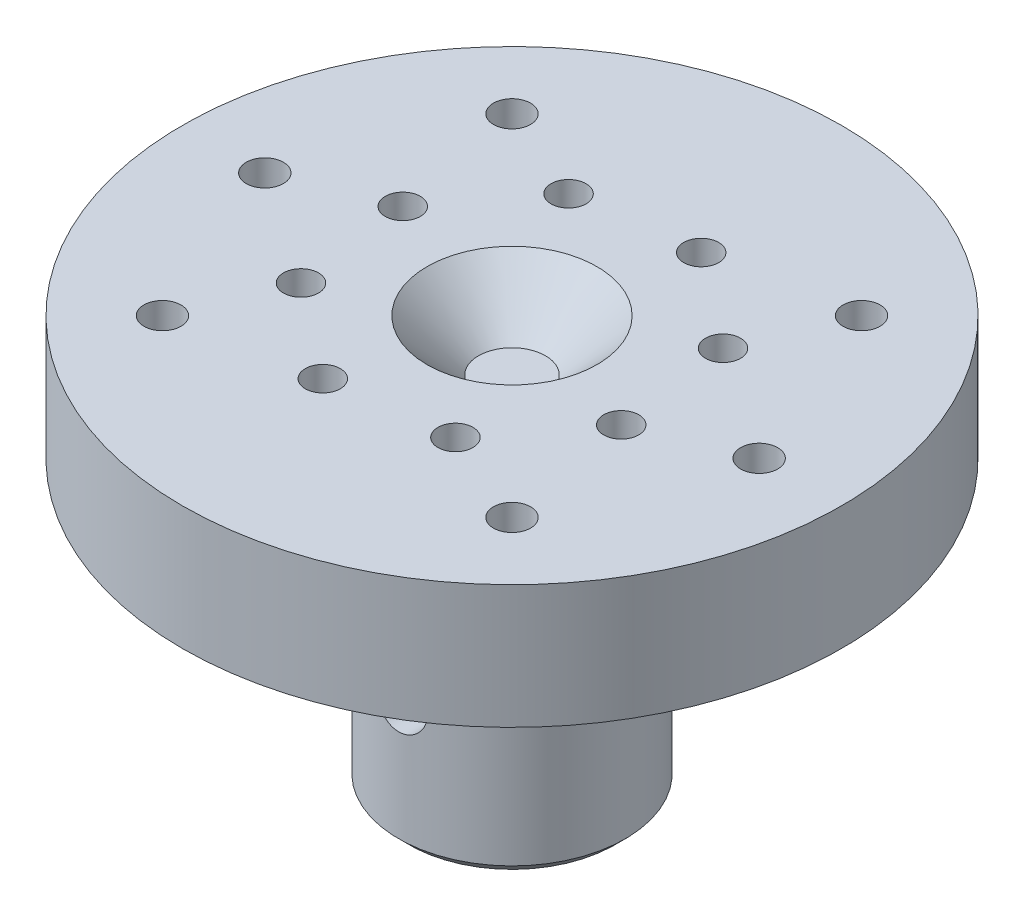
SolidWorks part; units mm, degrees
ref_plane "Front Plane" through (0, 0, 0) normal (0, 0, 1) x (1, 0, 0)
ref_plane "Top Plane" through (0, 0, 0) normal (0, 1, 0) x (1, 0, 0)
ref_plane "Right Plane" through (0, 0, 0) normal (1, 0, 0) x (0, 0, -1)
sketch "Sketch1" plane through (0, 0, 0) normal (0, 1, 0) x (1, 0, 0)
  circle A0 centre (0, 0) radius 8.25
  circle A1 centre (0, 0) radius 32
  dimension "D1" = 16.5
  dimension "D2" = 64
extrude "Boss-Extrude1" add sketch "Sketch1" along normal blind 12
sketch "Sketch2" plane through (0, 12, 0) normal (0, 1, 0) x (1, 0, 0)
  circle A0 centre (0, 21) radius 4
  circle A1 centre (0, 0) radius 21 construction
  circle A2 centre (18.1865, 10.5) radius 4
  circle A3 centre (18.1865, -10.5) radius 4
  circle A4 centre (0, -21) radius 4
  circle A5 centre (-18.1865, -10.5) radius 4
  circle A6 centre (-18.1865, 10.5) radius 4
  point P17 (0, 0)
  dimension "D1" = 8
  dimension "D2" = 42
  dimension "D3" = 6
extrude "Cut-Extrude1" [suppressed] cut sketch "Sketch2" against normal through all and the other way through all
hole_wizard "CSK for M3 Hex Socket Countersunk Head Screw1" positions "Sketch3" profile "Sketch4" countersink size "M3" standard "DIN" end condition up to next
sketch "Sketch3" plane through (0, 0, 0) normal (0, 1, 0) x (1, 0, 0)
  line L0 (0, 0) -> (32.7202, 18.891) construction
  circle A0 centre (0, 0) radius 15
  point P8 (12.9904, 7.5)
  point P14 (14.4889, -3.8823)
  point P15 (7.5, -12.9904)
  point P16 (-3.8823, -14.4889)
  point P17 (-12.9904, -7.5)
  point P18 (-14.4889, 3.8823)
  point P19 (-7.5, 12.9904)
  point P20 (3.8823, 14.4889)
  dimension "D2" = 30
  dimension "D1" = 30
  dimension "D3" = 8
sketch "Sketch4" plane through (3.8823, 0, -14.4889) normal (1, 0, 0) x (0, 0, -1)
  line L0 (0, 0) -> (0, 12)
  line L1 (0, 12) -> (1.7, 12)
  line L2 (1.7, 12) -> (1.7, 1.05)
  line L3 (1.7, 1.05) -> (2.75, 0)
  line L5 (2.75, 0) -> (0, 0)
  line L6 (-1.7, 1.05) -> (-2.75, 0) construction
  line L11 (0, -6.35) -> (0, 107.95) construction
  dimension "Thru Hole Dia." = 3.4
  dimension "Thru Hole Depth" = 12
  dimension "Near C'Sink Dia." = 5.5
  dimension "Near C'Sink Angle" = 90
hole_wizard "CSK for M3 Hex Socket Countersunk Head Screw2" positions "Sketch5" profile "Sketch7" countersink size "M3" standard "DIN"
sketch "Sketch5" plane through (0, 0, 0) normal (0, -1, 0) x (-1, 0, 0)
  circle A0 centre (0, 0) radius 24
  point P6 (-24, 0)
  point P14 (-16.9706, 16.9706)
  point P16 (16.9706, 16.9706)
  point P17 (24, 0)
  point P18 (16.9706, -16.9706)
  point P22 (-16.9706, -16.9706)
  point P25 (0, 24) [skipped]
  point P27 (0, -24) [skipped]
  dimension "D1" = 48
  dimension "D2" = 8
sketch "Sketch7" plane through (16.9706, 0, 16.9706) normal (1, 0, 0) x (0, 0, -1)
  line L0 (0, 0) -> (0, 12)
  line L1 (0, 12) -> (1.8, 12)
  line L2 (1.8, 12) -> (1.8, 1.67)
  line L3 (1.8, 1.67) -> (3.47, 0)
  line L5 (3.47, 0) -> (0, 0)
  line L6 (-1.8, 1.67) -> (-3.47, 0) construction
  line L11 (0, -6.35) -> (0, 107.95) construction
  dimension "Thru Hole Dia." = 3.6
  dimension "Thru Hole Depth" = 12
  dimension "Near C'Sink Dia." = 6.94
  dimension "Near C'Sink Angle" = 90
hole_wizard "Ø3.2 (3.2) Diameter Hole1" [suppressed] positions "Sketch8" profile "Sketch9" hole size "Ø3.2" standard "DIN"
sketch "Sketch8" plane through (0, 0, 0) normal (0, -1, 0) x (-1, 0, 0)
  circle A0 centre (0, 0) radius 15
  point P5 (0, 15)
  point P12 (12.9904, 7.5)
  point P13 (12.9904, -7.5)
  point P14 (0, -15)
  point P15 (-12.9904, -7.5)
  point P16 (-12.9904, 7.5)
  dimension "D1" = 30
  dimension "D2" = 6
sketch "Sketch9" plane through (12.9904, 0, -7.5) normal (1, 0, 0) x (0, 0, -1)
  line L0 (0, 0) -> (0, 2)
  line L1 (0, 2) -> (1.6, 2)
  line L2 (1.6, 2) -> (1.6, 0)
  line L5 (1.6, 0) -> (0, 0)
  line L11 (0, -6.35) -> (0, 107.95) construction
  dimension "Thru Hole Dia." = 3.2
  dimension "Thru Hole Depth" = 2
sketch "Sketch10" plane through (0, 0, 0) normal (0, -1, 0) x (1, 0, 0)
  circle A0 centre (0, 0) radius 19
  circle A1 centre (-3.8823, 14.4889) radius 2.75 construction
  circle A2 centre (-12.9904, 7.5) radius 2.75 construction
  circle A3 centre (-14.4889, -3.8823) radius 2.75 construction
  circle A4 centre (-7.5, -12.9904) radius 2.75 construction
  circle A5 centre (3.8823, -14.4889) radius 2.75 construction
  circle A6 centre (12.9904, -7.5) radius 2.75 construction
  circle A7 centre (14.4889, 3.8823) radius 2.75 construction
  circle A8 centre (7.5, 12.9904) radius 2.75 construction
  circle A9 centre (7.5, 12.9904) radius 2.75
  circle A10 centre (14.4889, 3.8823) radius 2.75
  circle A11 centre (12.9904, -7.5) radius 2.75
  circle A12 centre (3.8823, -14.4889) radius 2.75
  circle A13 centre (-7.5, -12.9904) radius 2.75
  circle A14 centre (-14.4889, -3.8823) radius 2.75
  circle A15 centre (-12.9904, 7.5) radius 2.75
  circle A16 centre (-3.8823, 14.4889) radius 2.75
  dimension "D1" = 38
extrude "Boss-Extrude2" add sketch "Sketch10" along normal blind 27.5 and the other way blind 7
sketch "Sketch11" plane through (0, -27.5, 0) normal (0, -1, 0) x (1, 0, 0)
  circle A0 centre (0, 0) radius 19 construction
  circle A1 centre (0, 0) radius 19
  circle A2 centre (0, 0) radius 11
  dimension "D1" = 22
extrude "Cut-Extrude2" cut sketch "Sketch11" against normal blind 25.5
chamfer "Chamfer1" distance 5 angle 45 1 edges at (0, 7, -8.25)
chamfer "Chamfer2" distance 1 angle 45 1 edges at (0, -27.5, -11)
ref_plane "Plane1" through (0, 0, 15) normal (0, 0, 1) x (1, 0, 0)
ref_plane "Plane2" through (0, 0, -15) normal (0, 0, 1) x (1, 0, 0)
hole_wizard "Ø4.2 (4.2) Diameter Hole1" positions "Sketch14" profile "Sketch16" hole size "Ø4.2" standard "DIN" end condition through all
sketch "Sketch14" plane through (0, 0, 15) normal (0, 0, 1) x (1, 0, 0)
  line L0 (0, -27.5) -> (0, -15)
  line L1 (-10, -27.5) -> (10, -27.5) construction
  point P2 (0, -15)
  dimension "D1" = 12.5
sketch "Sketch16" plane through (0, -15, 15) normal (1, 0, 0) x (0, -1, 0)
  line L0 (0, 0) -> (0, 47)
  line L1 (0, 47) -> (2.1, 47)
  line L2 (2.1, 47) -> (2.1, 0)
  line L5 (2.1, 0) -> (0, 0)
  line L11 (0, -6.35) -> (0, 107.95) construction
  dimension "Thru Hole Dia." = 4.2
  dimension "Thru Hole Depth" = 47
sketch "Sketch27" plane through (0, 0, 15) normal (0, 0, 1) x (1, 0, 0)
  circle A0 centre (0, -15) radius 2.5
  dimension "D1" = 5
extrude "Cut-Extrude3" cut sketch "Sketch27" against normal blind 8.5
sketch "Sketch28" plane through (0, 0, -15) normal (0, 0, 1) x (1, 0, 0)
  circle A0 centre (0, -15) radius 2.5
  circle A1 centre (0, -15) radius 2.1 construction
  dimension "D1" = 5
extrude "Cut-Extrude4" cut sketch "Sketch28" along normal blind 8.5
